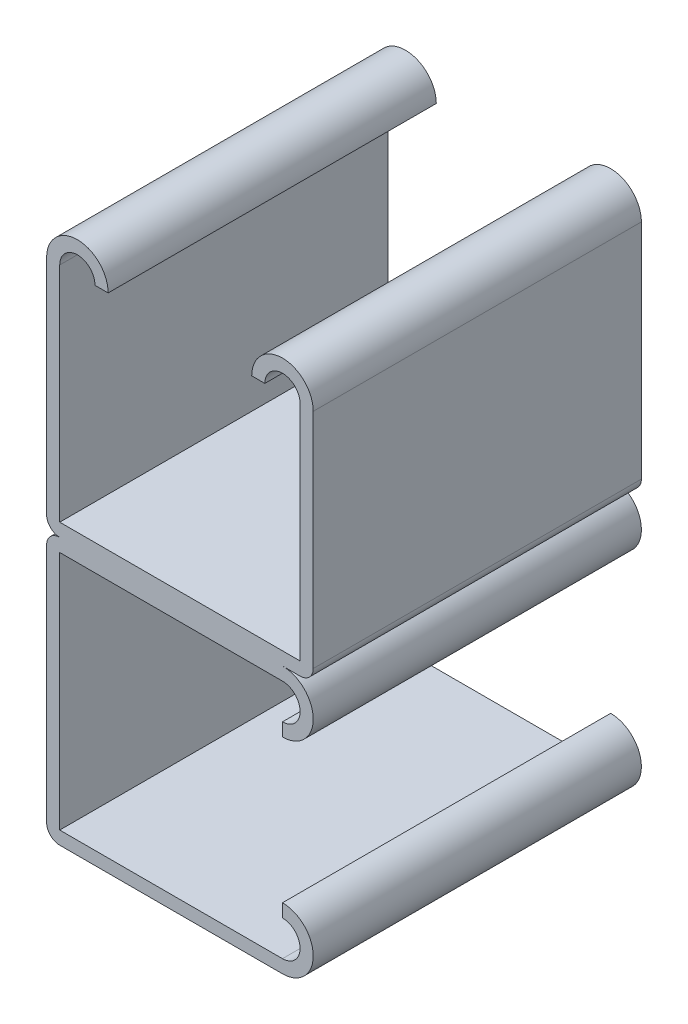
SolidWorks part; units mm, degrees
note: '?' marks a value the reader was unsure of.
ref_plane "Plane1" through (0, 0, 0) normal (0, 0, 1) x (1, 0, 0)
ref_plane "Plane2" through (0, 0, 0) normal (0, 1, 0) x (1, 0, 0)
ref_plane "Plane3" through (0, 0, 0) normal (1, 0, 0) x (0, 0, -1)
sketch "Sketch1" plane through (0, 0, 0) normal (0, 0, 1) x (1, 0, 0)
  line L0 (0, 18.2563) -> (0, 1.016)
  line L1 (1.016, 0) -> (19.6215, 0)
  line L2 (20.6375, 1.016) -> (20.6375, 18.2562)
  line L3 (16.891, 18.2562) -> (15.875, 18.2562)
  line L4 (4.7625, 18.2563) -> (3.7465, 18.2563)
  line L6 (1.016, 18.2563) -> (1.016, 1.016)
  line L7 (1.016, 1.016) -> (19.6215, 1.016)
  line L8 (19.6215, 1.016) -> (19.6215, 18.2562)
  line L10 (-4.7625, 20.6375) -> (46.0375, 20.6375) construction
  arc A0 (20.6375, 18.2562) -> (15.875, 18.2562) centre (18.2563, 18.2562) ccw
  arc A1 (0, 18.2563) -> (4.7625, 18.2563) centre (2.3813, 18.2563) cw
  arc A2 (1.016, 0) -> (0, 1.016) centre (1.016, 1.016) cw
  arc A3 (19.6215, 0) -> (20.6375, 1.016) centre (19.6215, 1.016) ccw
  arc A4 (1.016, 18.2563) -> (3.7465, 18.2563) centre (2.3813, 18.2563) cw
  arc A5 (19.6215, 18.2562) -> (16.891, 18.2562) centre (18.2563, 18.2562) ccw
  dimension "D2" = 20.6375
  dimension "D3" = 4.7625
  dimension "D4" = 11.1125
  dimension "D5" = 4.7625
  dimension "D6" = 1.016
extrude "Base-Extrude" add sketch "Sketch1" along normal mid plane 25.4
ref_axis "Axis1" through (0, 0, -50) along (0, 0, 1)?
pattern_circular "CirPattern1" count 2 every 270 about axis through (0, 0, 0) along (0, 0, 1) of "Base-Extrude"
equation "\"D1@Sketch1\" = \"gauge@Sketch1\""
